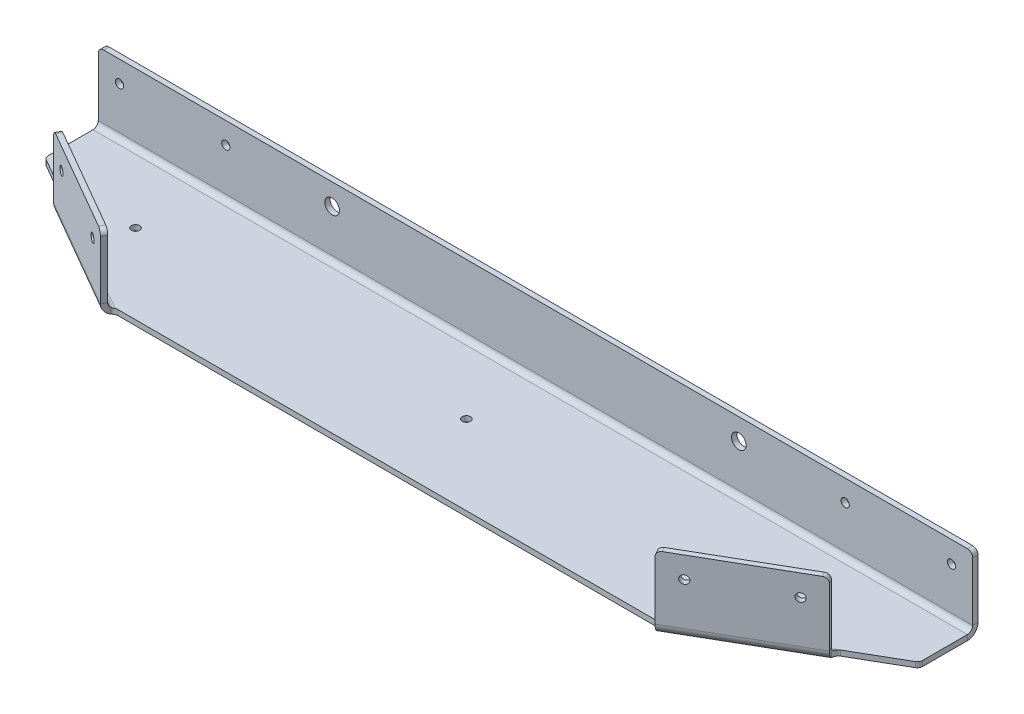
SolidWorks part; units mm, degrees
note: The reader was unsure of these and kept them because the rebuilt part matched: flange length of "Edge-Flange1".
material "5052-H32"
ref_plane "Front Plane" through (0, 0, 0) normal (0, 0, 1) x (1, 0, 0)
ref_plane "Top Plane" through (0, 0, 0) normal (0, 1, 0) x (1, 0, 0)
ref_plane "Right Plane" through (0, 0, 0) normal (1, 0, 0) x (0, 0, -1)
sketch "Sketch1" plane through (0, 0, 0) normal (0, 1, 0) x (1, 0, 0)
  line L0 (0, 0) -> (-522.2875, 0)
  line L2 (-423.6088, -85.5472) -> (-98.6787, -85.5472)
  line L4 (-522.2875, 0) -> (-522.2875, -28.575)
  line L5 (-522.2875, -28.575) -> (-423.6088, -85.5472)
  line L6 (-98.6787, -85.5472) -> (0, -28.575)
  line L7 (0, -28.575) -> (0, 0)
  dimension "D1" = 522.2875
  dimension "D2" = 120
  dimension "D3" = 85.5472
  dimension "D4" = 28.575
base flange "Base-Flange1" sketch "Sketch1" thickness 3.175 reverse thickness direction no parameters "D1"=3.175
edge flange "Edge-Flange1" sketch "Sketch12" flange profiles "Sketch12", "Sketch13", "Sketch14" flange angle 90 flange length 41.275 flange position bend outside bend radius 3.175 thickness 3.175 relief rectangular parameters "D6"=10, "D8"=1
sketch "Sketch12" plane through (0, 0, 0) normal (0, 0, -1) x (-1, 0, 0)
  line L0 (0, 0) -> (522.2875, 0) construction
  line L1 (0, 0) -> (522.2875, 0)
  line L2 (0, 0) -> (0, 41.275)
  line L3 (0, 41.275) -> (522.2875, 41.275)
  line L4 (522.2875, 41.275) -> (522.2875, 0)
sketch "Sketch13" plane through (-142.9452, 0, 247.5884) normal (-0.5, 0, 0.866) x (0.866, 0, 0.5)
  line L0 (-438.0267, 0) -> (-324.0823, 0) construction
  line L1 (-438.0267, 0) -> (-324.0823, 0)
  line L2 (-438.0267, 0) -> (-438.0267, 41.275)
  line L3 (-438.0267, 41.275) -> (-324.0823, 41.275)
  line L4 (-324.0823, 41.275) -> (-324.0823, 0)
sketch "Sketch14" plane through (12.3733, 0, 21.4313) normal (0.5, 0, 0.866) x (0.866, 0, -0.5)
  line L0 (-128.2319, 0) -> (-14.2875, 0) construction
  line L1 (-128.2319, 0) -> (-14.2875, 0)
  line L2 (-128.2319, 0) -> (-128.2319, 41.275)
  line L3 (-128.2319, 41.275) -> (-14.2875, 41.275)
  line L4 (-14.2875, 41.275) -> (-14.2875, 0)
bend "EdgeBend1" bend radius 3.175 bend angle 90 parameters "D5"=1
bend "EdgeBend2" bend radius 3.175 bend angle 90 parameters "D5"=2
bend "EdgeBend3" bend radius 3.175 bend angle 90 parameters "D5"=3
sketch "Sketch15" plane through (-146.1202, 0, 253.0876) normal (-0.5, 0, 0.866) x (0.866, 0, 0.5)
  line L0 (-438.0267, -3.175) -> (-324.0823, -3.175) construction
  line L1 (-438.0267, 41.275) -> (-400.3814, 41.275)
  line L2 (-438.0267, 41.275) -> (-438.0267, -3.175)
  line L3 (-438.0267, -3.175) -> (-400.3814, -3.175)
  line L4 (-400.3814, 41.275) -> (-400.3814, -3.175)
  line L6 (-324.0823, 41.275) -> (-438.0267, 41.275) construction
  line L11 (-324.0823, 3.175) -> (-324.0823, 41.275) construction
  circle A0 centre (-387.6814, 28.575) radius 2.4575
  circle A1 centre (-336.8814, 28.575) radius 2.4574
  dimension "D5" = 4.9149
  dimension "D1" = 37.6453
  dimension "D2" = 12.7
  dimension "D3" = 12.7
  dimension "D4" = 12.7991
extrude "Cut-Extrude1" cut sketch "Sketch15" against normal blind 6.35 normal cut yes
sketch "Sketch16" plane through (15.5483, 0, 26.9305) normal (0.5, 0, 0.866) x (0.866, 0, -0.5)
  line L0 (-128.2319, -3.175) -> (-14.2875, -3.175) construction
  line L1 (-14.2875, 41.275) -> (-51.9328, 41.275)
  line L2 (-14.2875, 41.275) -> (-14.2875, -3.175)
  line L3 (-14.2875, -3.175) -> (-51.9328, -3.175)
  line L4 (-51.9328, 41.275) -> (-51.9328, -3.175)
  line L5 (-128.2319, 41.275) -> (-128.2319, 3.175) construction
  line L10 (-14.2875, 41.275) -> (-128.2319, 41.275) construction
  circle A0 centre (-64.6328, 28.575) radius 2.4574
  circle A1 centre (-115.4328, 28.575) radius 2.4574
  dimension "D5" = 4.9149
  dimension "D1" = 37.6453
  dimension "D2" = 12.7991
  dimension "D3" = 12.7
  dimension "D4" = 12.7
extrude "Cut-Extrude2" cut sketch "Sketch16" against normal blind 6.35 normal cut yes
sketch "Sketch17" plane through (0, 0, -6.35) normal (0, 0, -1) x (-1, 0, 0)
  line L0 (522.2875, 3.175) -> (522.2875, 41.275) construction
  line L1 (522.2875, 41.275) -> (0, 41.275) construction
  line L2 (0, 41.275) -> (0, 3.175) construction
  circle A0 centre (509.6231, 28.575) radius 2.4575
  circle A1 centre (12.6644, 28.575) radius 2.4574
  circle A2 centre (76.1644, 28.575) radius 2.4574
  circle A3 centre (446.1231, 28.575) radius 2.4574
  circle A4 centre (139.6644, 28.575) radius 4.3688
  circle A5 centre (382.6231, 28.575) radius 4.3688
  dimension "D3" = 4.9149
  dimension "D7" = 8.7376
  dimension "D1" = 12.6644
  dimension "D2" = 12.7
  dimension "D4" = 12.6644
  dimension "D5" = 63.5
  dimension "D6" = 63.5
  dimension "D8" = 63.5
  dimension "D9" = 63.5
extrude "Cut-Extrude3" cut sketch "Sketch17" against normal blind 3.175 normal cut yes
fillet "Fillet1" radius 3.175 14 edges at (-489.6857, -1.5875, 47.3977) (-490.8082, 0.9299, 49.342) (0, -1.5875, 28.575) (-98.6787, -1.5875, 85.5472) (-423.6088, -1.5875, 85.5472) (-522.2875, -1.5875, 28.575) (-30.2206, 41.275, 51.5221) (-32.6018, -1.5875, 47.3977) (-31.4793, 0.9299, 49.342) (0, 41.275, -4.7625) (-522.2875, 41.275, -4.7625) (-425.99, 41.275, 89.6716) (-96.2975, 41.275, 89.6716) (-492.0669, 41.275, 51.5221)
sketch "Sketch18" plane through (0, -3.175, 0) normal (0, -1, 0) x (1, 0, 0)
  line L0 (-522.2875, -6.35) -> (0, -6.35) construction
  line L1 (-522.2875, 0) -> (-522.2875, 26.7419) construction
  line L2 (0, 26.7419) -> (0, 0) construction
  circle A0 centre (-458.7875, 38.1) radius 2.4575
  circle A1 centre (-261.1438, 38.1) radius 2.4574
  circle A2 centre (-63.5, 38.1) radius 2.4575
  dimension "D1" = 4.9149
  dimension "D2" = 44.45
  dimension "D3" = 63.5
  dimension "D4" = 63.5
  dimension "D5" = 261.1438
extrude "Cut-Extrude4" cut sketch "Sketch18" against normal blind 3.175 normal cut yes
sketch "Bend-Lines1" [suppressed] plane through (0, 0, 0) normal (0, 1, 0) x (1, 0, 0)
sketch "Bounding-Box1" [suppressed] plane through (0, 0, 0) normal (0, 1, 0) x (1, 0, 0)
sheet metal parameters "Sheet-Metal1" thickness 3.175 parameters "D1"=3.175
flat pattern "Flat-Pattern1" [suppressed]
sketch "Bend-Lines2" plane through (0, 0, 0) normal (0, 1, 0) x (1, 0, 0)
sketch3d "Bounding-Box2" [suppressed]
  line L0 (0, -88.9, 0) -> (522.2875, -88.9, 0) construction
  line L1 (0, 0, 0) -> (522.2875, 0, 0) construction
  line L2 (0, -88.9, 0) -> (0, 0, 0) construction
  line L3 (522.2875, -88.9, 0) -> (522.2875, 0, 0) construction
sheet metal parameters "Sheet-Metal2" thickness 3.175 parameters "D1"=3.175
flat pattern "Flat-Pattern1"
sketch "Bend-Lines2" plane through (0, 0, 0) normal (0, 1, 0) x (1, 0, 0)
  line L0 (-97.1165, -88.9643) -> (1.8702, -31.8143) construction
  line L1 (-524.1577, -31.8143) -> (-425.171, -88.9643) construction
  line L2 (0, 3.7405) -> (-522.2875, 3.7405) construction
  line L3 (-97.1165, -88.9643) -> (1.8702, -31.8143) construction
  line L4 (-524.1577, -31.8143) -> (-425.171, -88.9643) construction
  line L5 (0, 3.7405) -> (-522.2875, 3.7405) construction
sketch3d "Bounding-Box2" [suppressed]
  line L0 (22.7905, -125.1992, 0) -> (-545.078, -125.1992, 0) construction
  line L1 (22.7905, 45.5809, 0) -> (-545.078, 45.5809, 0) construction
  line L2 (22.7905, -125.1992, 0) -> (22.7905, 45.5809, 0) construction
  line L3 (-545.078, -125.1992, 0) -> (-545.078, 45.5809, 0) construction
bend of the flat pattern "Flatten-<EdgeBend1>1"
bend of the flat pattern "Flatten-<EdgeBend2>1"
bend of the flat pattern "Flatten-<EdgeBend3>1"
sheet metal parameters "Sheet-Metal3" thickness 3.175 parameters "D1"=3.175
flat pattern "Flat-Pattern1"
sketch "Bend-Lines2" plane through (0, 0, 0) normal (0, 1, 0) x (1, 0, 0)
  line L0 (-97.1165, -88.9643) -> (1.8702, -31.8143) construction
  line L1 (-491.5559, -50.637) -> (-425.171, -88.9643) construction
  line L2 (0, 3.7405) -> (-522.2875, 3.7405) construction
  line L3 (-97.1165, -88.9643) -> (1.8702, -31.8143) construction
  line L4 (-491.5559, -50.637) -> (-425.171, -88.9643) construction
  line L5 (0, 3.7405) -> (-522.2875, 3.7405) construction
sketch3d "Bounding-Box2" [suppressed]
  line L0 (22.7905, -125.1992, 0) -> (-522.2875, -125.1992, 0) construction
  line L1 (22.7905, 45.5809, 0) -> (-522.2875, 45.5809, 0) construction
  line L2 (22.7905, -125.1992, 0) -> (22.7905, 45.5809, 0) construction
  line L3 (-522.2875, -125.1992, 0) -> (-522.2875, 45.5809, 0) construction
bend of the flat pattern "Flatten-<EdgeBend1>1"
bend of the flat pattern "Flatten-<EdgeBend2>1"
bend of the flat pattern "Flatten-<EdgeBend3>1"
sheet metal parameters "Sheet-Metal4" thickness 3.175 parameters "D1"=3.175
flat pattern "Flat-Pattern1"
sketch "Bend-Lines2" plane through (0, 0, 0) normal (0, 1, 0) x (1, 0, 0)
  line L0 (-96.8085, -88.7865) -> (-30.7316, -50.637) construction
  line L1 (-491.5559, -50.637) -> (-425.479, -88.7865) construction
  line L2 (0, 3.7405) -> (-522.2875, 3.7405) construction
  line L3 (-96.8085, -88.7865) -> (-30.7316, -50.637) construction
  line L4 (-491.5559, -50.637) -> (-425.479, -88.7865) construction
  line L5 (0, 3.7405) -> (-522.2875, 3.7405) construction
sketch3d "Bounding-Box2" [suppressed]
  line L0 (0, -125.0214, 0) -> (-522.2875, -125.0214, 0) construction
  line L1 (0, 45.5809, 0) -> (-522.2875, 45.5809, 0) construction
  line L2 (0, -125.0214, 0) -> (0, 45.5809, 0) construction
  line L3 (-522.2875, -125.0214, 0) -> (-522.2875, 45.5809, 0) construction
bend of the flat pattern "Flatten-<EdgeBend1>1"
bend of the flat pattern "Flatten-<EdgeBend2>1"
bend of the flat pattern "Flatten-<EdgeBend3>1"
sheet metal parameters "Sheet-Metal5" thickness 3.175 parameters "D1"=3.175
flat pattern "Flat-Pattern1"
sketch "Bend-Lines2" plane through (0, 0, 0) normal (0, 1, 0) x (1, 0, 0)
  line L0 (-96.8085, -88.7865) -> (-30.7316, -50.637) construction
  line L1 (-491.5559, -50.637) -> (-425.479, -88.7865) construction
  line L2 (0, 3.7405) -> (-522.2875, 3.7405) construction
  line L3 (-96.8085, -88.7865) -> (-30.7316, -50.637) construction
  line L4 (-491.5559, -50.637) -> (-425.479, -88.7865) construction
  line L5 (0, 3.7405) -> (-522.2875, 3.7405) construction
sketch3d "Bounding-Box2" [suppressed]
  line L0 (0, -125.0214, 0) -> (-522.2875, -125.0214, 0) construction
  line L1 (0, 45.5809, 0) -> (-522.2875, 45.5809, 0) construction
  line L2 (0, -125.0214, 0) -> (0, 45.5809, 0) construction
  line L3 (-522.2875, -125.0214, 0) -> (-522.2875, 45.5809, 0) construction
bend of the flat pattern "Flatten-<EdgeBend1>1"
bend of the flat pattern "Flatten-<EdgeBend2>1"
bend of the flat pattern "Flatten-<EdgeBend3>1"
sheet metal parameters "Sheet-Metal6" thickness 3.175 parameters "D1"=3.175
flat pattern "Flat-Pattern1"
sketch "Bend-Lines2" plane through (0, 0, 0) normal (0, 1, 0) x (1, 0, 0)
  line L0 (-96.8085, -88.7865) -> (-30.7316, -50.637) construction
  line L1 (-491.5559, -50.637) -> (-425.479, -88.7865) construction
  line L2 (0, 3.7405) -> (-522.2875, 3.7405) construction
  line L3 (-96.8085, -88.7865) -> (-30.7316, -50.637) construction
  line L4 (-491.5559, -50.637) -> (-425.479, -88.7865) construction
  line L5 (0, 3.7405) -> (-522.2875, 3.7405) construction
sketch3d "Bounding-Box2" [suppressed]
  line L0 (0, -125.0214, 0) -> (-522.2875, -125.0214, 0) construction
  line L1 (0, 45.5809, 0) -> (-522.2875, 45.5809, 0) construction
  line L2 (0, -125.0214, 0) -> (0, 45.5809, 0) construction
  line L3 (-522.2875, -125.0214, 0) -> (-522.2875, 45.5809, 0) construction
bend of the flat pattern "Flatten-<EdgeBend1>1"
bend of the flat pattern "Flatten-<EdgeBend2>1"
bend of the flat pattern "Flatten-<EdgeBend3>1"
